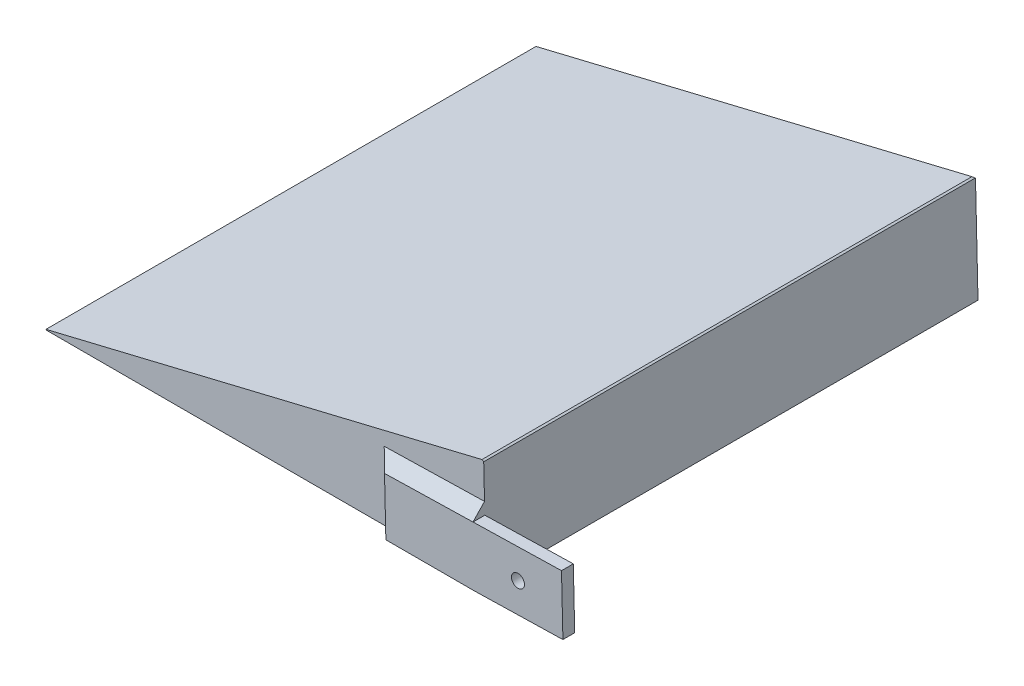
SolidWorks part; units mm, degrees
ref_plane "Front Plane" through (0, 0, 0) normal (0, 0, 1) x (1, 0, 0)
ref_plane "Top Plane" through (0, 0, 0) normal (0, 1, 0) x (1, 0, 0)
ref_plane "Right Plane" through (0, 0, 0) normal (1, 0, 0) x (0, 0, -1)
sketch "Sketch1" plane through (0, 0, 0) normal (0, 0, 1) x (1, 0, 0)
  line L0 (0, 0) -> (-499.8557, 0) construction
  line L1 (0, 0) -> (50, 0)
  line L2 (0, 0) -> (0, 48)
  line L3 (0, 48) -> (50, 48)
  line L4 (50, 0) -> (50, 48)
  line L5 (-499.8557, 0) -> (-500.7205, 35.9896)
  line L6 (-500.7205, 35.9896) -> (-0.8647, 48)
  line L7 (-499.8557, 0) -> (0, 12.0104)
  line L8 (0, 12.0104) -> (-0.8647, 48)
  line L9 (-500.3361, 19.9942) -> (-0.4804, 32.0046)
  line L10 (0, 32) -> (50, 32)
  line L11 (0, 12) -> (50, 12)
  dimension "D1" = 48
  dimension "D2" = 50
  dimension "D3" = 36
  dimension "D4" = 500
  dimension "D5" = 20
  dimension "D6" = 32
  dimension "D7" = 12
sketch "Sketch2" plane through (0, 0, 0) normal (0, 0, 1) x (1, 0, 0)
  line L0 (0, 12) -> (-40, 11.0493)
  line L1 (-499.8557, 0) -> (0, 12.0104) construction
  line L2 (-40, 11.0493) -> (-40, 0)
  line L3 (0, 0) -> (-499.8557, 0) construction
  line L4 (-40, 0) -> (0, 0)
  line L5 (0, 0) -> (0, 12)
  dimension "D1" = 40
sketch "Sketch3" plane through (0, 0, 0) normal (0, 0, 1) x (1, 0, 0)
  line L0 (-39.9885, 11.0496) -> (-40.4689, 31.0438)
  line L1 (-499.8557, 0) -> (0, 12.0104) construction
  line L2 (-500.3361, 19.9942) -> (-0.4804, 32.0046) construction
  line L3 (-40.4689, 31.0438) -> (-0.4804, 32.0046)
  line L4 (-0.4804, 32.0046) -> (39.5196, 32)
  line L5 (0, 32) -> (50, 32) construction
  line L7 (0, 12) -> (50, 12) construction
  line L8 (39.5196, 12) -> (0, 12)
  line L9 (0, 12) -> (-39.9885, 11.0496)
  line L10 (-40.2287, 21.0467) -> (-0.2402, 22.0075) construction
  line L11 (0, 12.0104) -> (-0.8647, 48) construction
  line L12 (39.5196, 32) -> (39.5196, 12)
  line L13 (39.5196, 22) -> (0, 22) construction
  line L14 (0, 0) -> (0, 48) construction
  circle A0 centre (19.7598, 22) radius 2.2
  circle A1 centre (-20.2344, 21.5271) radius 2.2
  dimension "D3" = 4.4
  dimension "D1" = 40
  dimension "D2" = 40
sketch "Sketch4" plane through (0, 0, 0) normal (0, 0, 1) x (1, 0, 0)
  line L0 (-499.8558, 0) -> (-769.6838, 0) construction
  line L1 (-500.7205, 35.9896) -> (-649.8557, 0)
  line L2 (-649.8557, 0) -> (-499.8557, 0)
  line L3 (-499.8557, 0) -> (-500.7205, 35.9896)
  dimension "D1" = 150
extrude "Boss-Extrude1" add sketch "Sketch4" against normal blind 166.6667
ref_plane "Plane1" through (0, 0, -3) normal (0, 0, 1) x (1, 0, 0)
sketch "Sketch6" plane through (0, 0, -3) normal (0, 0, 1) x (1, 0, 0)
  line L0 (-504.8572, 0) -> (-505.5702, 29.6757)
  line L1 (-649.8557, 0) -> (-499.8557, 0) construction
  line L2 (-505.5702, 29.6757) -> (-585.109, 10.4813)
  line L3 (-585.109, 10.4813) -> (-584.8572, 0)
  line L4 (-584.8572, 0) -> (-504.8572, 0)
  line L5 (-499.8557, 0) -> (-500.7205, 35.9896) construction
  line L6 (-500.7205, 35.9896) -> (-649.8557, 0) construction
  dimension "D1" = 5
  dimension "D2" = 5
  dimension "D3" = 80
extrude "Cut-Extrude1" cut sketch "Sketch6" against normal offset from surface (160.6667 mm away) 3 up to face at (-550.144, 11.9965, -166.6667)
sketch "Sketch7" plane through (-499.5673, -12.0035, 0) normal (0.9997, 0.024, 0) x (0, 0, -1)
  line L0 (20, 48.0069) -> (20, 12.0069) construction
  line L1 (166.6667, 48.0069) -> (0, 48.0069) construction
  line L2 (166.6667, 12.0069) -> (0, 12.0069) construction
  line L3 (0, 12.0069) -> (0, 48.0069) construction
  line L4 (20, 48.0069) -> (0, 12.0069) construction
  circle A0 centre (10, 30.0069) radius 2.75
  dimension "D2" = 5.5
  dimension "D1" = 20
extrude "Cut-Extrude2" [suppressed] cut sketch "Sketch7" against normal up to surface (5 mm away)
sketch "Sketch8" plane through (0, 0, 0) normal (0, 0, 1) x (1, 0, 0)
  line L0 (-500.3361, 19.9942) -> (-470.3448, 20.7149)
  line L1 (-500.3361, 19.9942) -> (-0.4804, 32.0046) construction
  line L2 (-470.3448, 20.7149) -> (-469.8644, 0.7206)
  line L3 (-499.8557, 0) -> (0, 12.0104) construction
  line L4 (-469.8644, 0.7206) -> (-499.8557, 0)
  line L5 (-499.8557, 0) -> (-529.8644, 0)
  line L6 (-649.8557, 0) -> (-499.8557, 0) construction
  line L7 (-529.8644, 0) -> (-530.3275, 19.2736)
  line L9 (-499.8557, 0) -> (-500.7205, 35.9896) construction
  line L10 (-500.3361, 19.9942) -> (-530.3275, 19.2736)
  dimension "D1" = 30
  dimension "D2" = 30
extrude "Boss-Extrude2" add sketch "Sketch8" along normal blind 4
sketch "Sketch9" plane through (0, 0, 4) normal (0, 0, 1) x (1, 0, 0)
  line L0 (-500.3361, 19.9942) -> (-469.8644, 0.7206) construction
  circle A0 centre (-485.1003, 10.3574) radius 2.2
  dimension "D1" = 4.4
extrude "Cut-Extrude3" cut sketch "Sketch9" against normal through all
sketch "Sketch10" plane through (0, 0, -166.6667) normal (0, 0, -1) x (-1, 0, 0)
  line L0 (527.1478, 12) -> (513.1478, 12) construction
  line L2 (649.8557, 0) -> (499.8557, 0) construction
  line L3 (499.8557, 0) -> (500.7205, 35.9896) construction
  circle A0 centre (513.1478, 12) radius 2.2
  circle A1 centre (527.1478, 12) radius 2.2
  dimension "D1" = 4.4
  dimension "D2" = 12
  dimension "D3" = 14
  dimension "D4" = 13
extrude "Cut-Extrude4" cut sketch "Sketch10" against normal up to surface (3 mm away) up to face at (-545.0984, 10.0393, -163.6667)
chamfer "Chamfer3" distance 0.6 angle 45 3 edges at (-649.8557, 0, -83.3333) (-500.7205, 35.9896, -83.3333) (-575.2881, 17.9948, -166.6667)
chamfer "Chamfer4" distance 1 angle 45 1 edges at (-649.8557, 0, -83.0333)
chamfer "Chamfer8" distance 4 angle 45 1 edges at (-515.3318, 19.6339, 0)
chamfer "Chamfer9" distance 4 angle 45 1 edges at (-530.144, 11.6362, 0)
